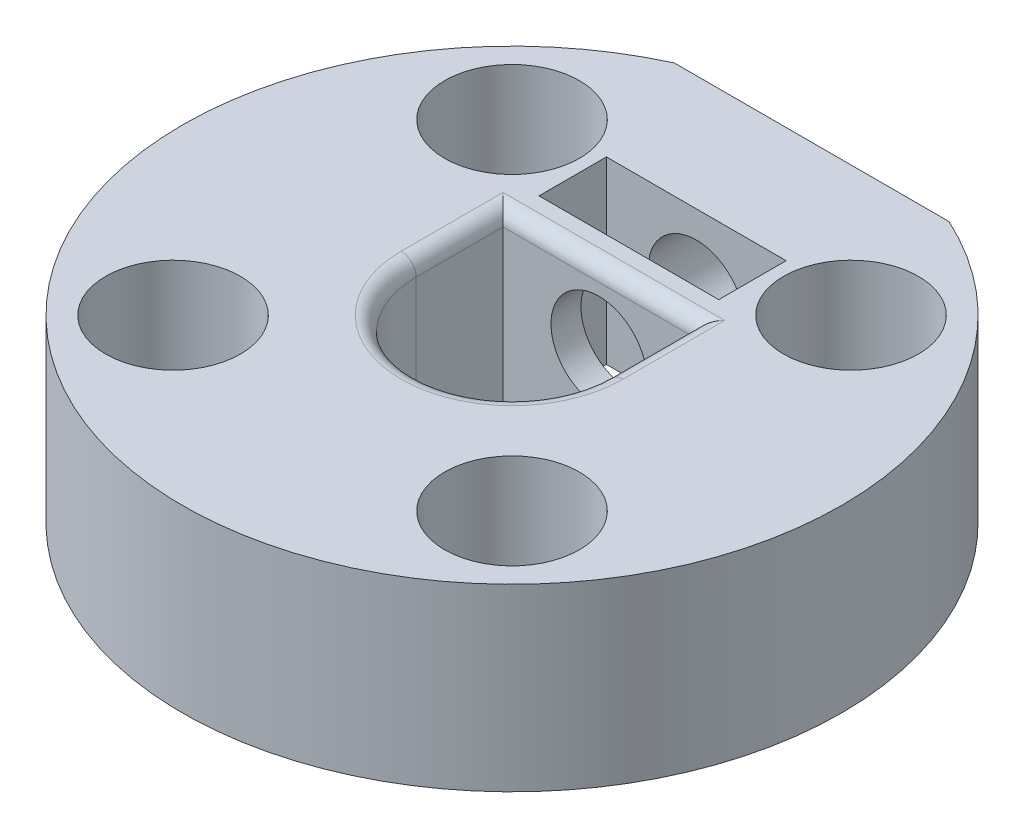
SolidWorks part; units mm, degrees
ref_plane "Plan de face" through (0, 0, 0) normal (0, 0, 1) x (1, 0, 0)
ref_plane "Plan de dessus" through (0, 0, 0) normal (0, 1, 0) x (1, 0, 0)
ref_plane "Plan de droite" through (0, 0, 0) normal (1, 0, 0) x (0, 0, -1)
sketch "Esquisse1" plane through (0, 0, 0) normal (0, 1, 0) x (1, 0, 0)
  line L1 (-3.2, 0) -> (-3.2, 2.9)
  line L2 (3.2, 0) -> (3.2, 2.9)
  line L3 (3.2, 2.9) -> (-3.2, 2.9)
  line L4 (4.5826, 10) -> (-4.5826, 10)
  arc A0 (-4.5826, 10) -> (4.5826, 10) centre (0, 0) ccw
  arc A1 (-3.2, 0) -> (3.2, 0) centre (0, 0) ccw
  point P10 (0, 2.9)
  dimension "D1" = 22
  dimension "D2" = 6.4
  dimension "D3" = 2.9
  dimension "D4" = 10
extrude "Boss.-Extru.1" add sketch "Esquisse1" along normal blind 6
hole_wizard "Chambrage pour vis à tête cylindrique à 6 pans creux (ou vis CHC) M21" positions "Esquisse2" profile "Esquisse3" counterbore size "M2" standard "Ansi Metric" end condition through all
sketch "Esquisse2" plane through (0, 6, 0) normal (0, 1, 0) x (1, 0, 0)
  line L0 (0, 0) -> (6.1221, 0) construction
  line L2 (0, 0) -> (9.471, 9.471) construction
  point P0 (5.6569, 5.6569)
  point P28 (5.6569, -5.6569)
  point P29 (-5.6569, -5.6569)
  point P30 (-5.6569, 5.6569)
  point P31 (0, 0)
  dimension "D1" = 8
  dimension "D3" = 45
  dimension "D2" = 4
sketch "Esquisse3" plane through (5.6569, 6, -5.6569) normal (1, 0, 0) x (0, 0, 1)
  line L0 (0, 0) -> (0, 6)
  line L1 (0, 6) -> (1.25, 6)
  line L3 (1.25, 6) -> (1.25, 4.5)
  line L4 (1.25, 4.5) -> (2.25, 4.5)
  line L5 (2.25, 4.5) -> (2.25, 0)
  line L7 (2.25, 0) -> (0, 0)
  line L11 (0, -6.35) -> (0, 107.95) construction
  dimension "Diamètre du perçage jusqu'au prochain" = 2.5
  dimension "Profondeur du perçage jusqu'au prochain" = 6
  dimension "Diamètre du chambrage" = 4.5
  dimension "Profondeur du chambrage" = 4.5
fillet "Congé1" radius 0.5 4 edges at (0, 6, 3.2) (-3.2, 6, -1.45) (3.2, 6, -1.45) (0, 6, -2.9)
sketch "Esquisse6" plane through (0, 0, 0) normal (0, 0, 1) x (1, 0, 0)
  line L0 (0, 0) -> (0, 6) construction
  line L1 (11, 6) -> (-11, 6) construction
  line L2 (11, 6) -> (-11, 6) construction
  circle A0 centre (0, 3.5) radius 1.6
  dimension "D1" = 3.2
  dimension "D2" = 2.5
extrude "Enlèv. mat.-Extru.1" cut sketch "Esquisse6" against normal through all
sketch "Esquisse7" plane through (0, 6, 0) normal (0, 1, 0) x (1, 0, 0)
  line L1 (-3, 3.9) -> (3, 3.9)
  line L2 (-3, 3.9) -> (-3, 6.15)
  line L3 (-3, 6.15) -> (3, 6.15)
  line L4 (3, 3.9) -> (3, 6.15)
  line L5 (-3, 3.9) -> (3, 6.15) construction
  line L6 (-3, 6.15) -> (3, 3.9) construction
  line L7 (3.2, 2.9) -> (-3.2, 2.9) construction
  point P0 (0, 5.025)
  dimension "D3" = 1
  dimension "D1" = 2.25
  dimension "D2" = 6
extrude "Enlèv. mat.-Extru.2" cut sketch "Esquisse7" against normal through all
